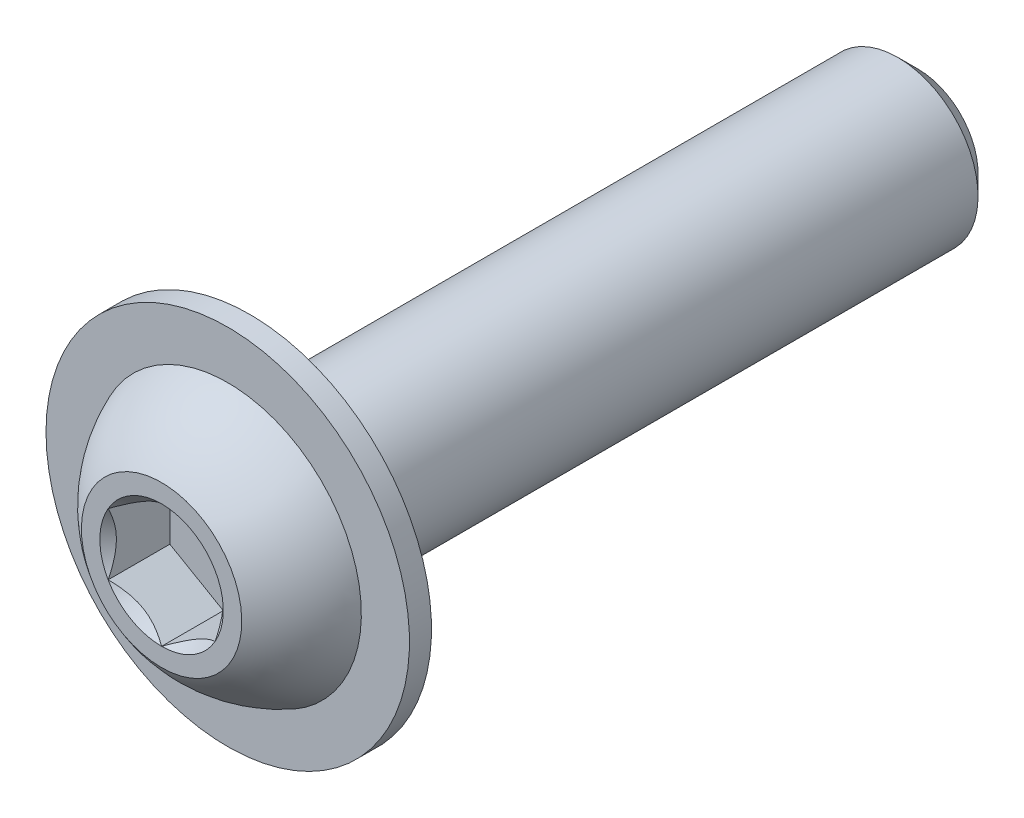
SolidWorks part; units mm, degrees
material "AISI 304"
ref_plane "Front" through (0, 0, 0) normal (0, 0, 1) x (1, 0, 0)
ref_plane "Top" through (0, 0, 0) normal (0, 1, 0) x (1, 0, 0)
ref_plane "Right" through (0, 0, 0) normal (1, 0, 0) x (0, 0, -1)
sketch "Sketch1" plane through (0, 0, 0) normal (1, 0, 0) x (0, 0, -1)
  line L2 (3.3, 3) -> (28.3, 3)
  line L3 (28.3, 3) -> (28.3, 0)
  line L4 (28.3, 0) -> (3.3, 0)
  line L6 (2.475, 5) -> (3.3, 5) construction
  line L7 (28.3, 3) -> (28.3, -3) construction
  line L8 (0, 0) -> (3.3, 0) construction
  line L9 (3.3, 5) -> (3.3, -5) construction
  line L11 (3.3, 3) -> (3.3, 0)
  line L13 (0, 2) -> (0, -2) construction
  line L14 (0, 2) -> (0, 3) construction
  line L15 (2.475, 5) -> (2.475, 6.8) construction
  line L16 (2.475, 6.8) -> (3.3, 6.8) construction
  line L17 (3.3, 6.8) -> (3.3, 5) construction
  line L18 (3.3, 6.8) -> (3.3, -6.8) construction
  arc A3 (0, 3) -> (2.475, 5) centre (4.4698, 0) cw construction
  dimension "D1" = 0.825
revolve "Revolve1" add sketch "Sketch1" angle 360 mid plane about L4
sketch "Sketch3" plane through (0, 0, -28.3) normal (0, 0, -1) x (-1, 0, 0)
  circle A0 centre (0, 0) radius 3
curve "Helix/Spiral1" pitch 1 height 26 turns 26
sketch "Sketch2" plane through (0, 0, 0) normal (1, 0, 0) x (0, 0, -1)
  line L0 (28.3, 3) -> (29.175, 3)
  line L1 (29.175, 3) -> (28.8, 2.3505)
  line L2 (28.8, 2.3505) -> (28.675, 2.3505)
  line L3 (28.675, 2.3505) -> (28.3, 3)
  line L4 (28.4875, 2.6752) -> (28.9875, 2.6752) construction
  dimension "D1" = 60
  dimension "D2" = 0.125
  dimension "D3" = 0.5
chamfer "Chamfer1" distance 0.75 angle 45 1 edges at (0, 3, -28.3)
sweep "Cut-Sweep1" [suppressed] cut profiles "Sketch2" path "Helix/Spiral1"
sketch "Sketch7" plane through (0, 0, 0) normal (1, 0, 0) x (0, 0, -1)
  line L6 (2.475, 5) -> (3.3, 5) construction
  line L8 (0, 0) -> (3.3, 0) construction
  line L11 (3.3, 5) -> (3.3, -5) construction
  line L12 (2.475, 5) -> (3.3, 5)
  line L13 (0, 0) -> (3.3, 0)
  line L14 (0, 2) -> (0, -2) construction
  line L15 (3.3, 5) -> (3.3, 0)
  line L16 (0, 3) -> (0, 0)
  arc A2 (2.475, 5) -> (0, 3) centre (4.4698, 0) ccw construction
  arc A3 (2.475, 5) -> (0, 3) centre (4.4698, 0) ccw
revolve "Revolve2" add sketch "Sketch7" angle 360 mid plane about L13
sketch "Sketch11" plane through (0, 0, -3.3) normal (0, 0, -1) x (-1, 0, 0)
  circle A0 centre (0, 0) radius 6.8
extrude "Boss-Extrude3" add sketch "Sketch11" against normal up to vertex (0.825 mm away) up to point (0, 5, -2.475)
sketch "Sketch5" plane through (0, 0, 0) normal (0, 0, 1) x (1, 0, 0)
  line L1 (2, -1.1547) -> (2, 1.1547)
  line L2 (2, 1.1547) -> (0, 2.3094)
  line L3 (0, 2.3094) -> (-2, 1.1547)
  line L4 (-2, 1.1547) -> (-2, -1.1547)
  line L5 (-2, -1.1547) -> (0, -2.3094)
  line L6 (0, -2.3094) -> (2, -1.1547)
  circle A0 centre (0, 0) radius 2 construction
extrude "Cut-Extrude2" cut sketch "Sketch5" against normal blind 2.31
sketch "Sketch6" plane through (0, 0, 0) normal (0, 0, 1) x (1, 0, 0)
  circle A0 centre (0, 0) radius 2.3094
extrude "Cut-Extrude3" cut sketch "Sketch6" against normal blind 2.31 draft 45
sketch "Sketch9" [suppressed] plane through (0, 0, -5.0546) normal (0, 0, 1) x (1, 0, 0)
  circle A2 centre (0, 0) radius 4.7625
extrude "Boss-Extrude2" [suppressed] add sketch "Sketch9" against normal offset from surface (6.35 mm away) 31.75
sketch "Sketch10" plane through (0, 0, 0) normal (1, 0, 0) x (0, 0, -1)
  line L0 (28.3, 3) -> (28.3, -3) construction
  point P0 (26.8, -3)
  dimension "D1" = 1.5
equation "\"D3@Helix/Spiral1\" = \"Lg@Sketch1\" + \"D4@Helix/Spiral1\""
equation "\"D2@Sketch2\" = \"D4@Helix/Spiral1\" * .125"
equation "\"D3@Sketch2\" = \"D4@Helix/Spiral1\" * .5"
equation "\"D1@Chamfer1\" = \"D4@Helix/Spiral1\" * .75"
equation "\"D1@Cut-Extrude2\" = \"Head Ht@Sketch1\" * .7"
equation "\"D1@Sketch1\" = \"Head Ht@Sketch1\" * .25"
equation "\"D1@Sketch10\" = \"D4@Helix/Spiral1\" * 1.5"
equation "\"D1@Cut-Extrude3\" = \"D1@Cut-Extrude2\""
